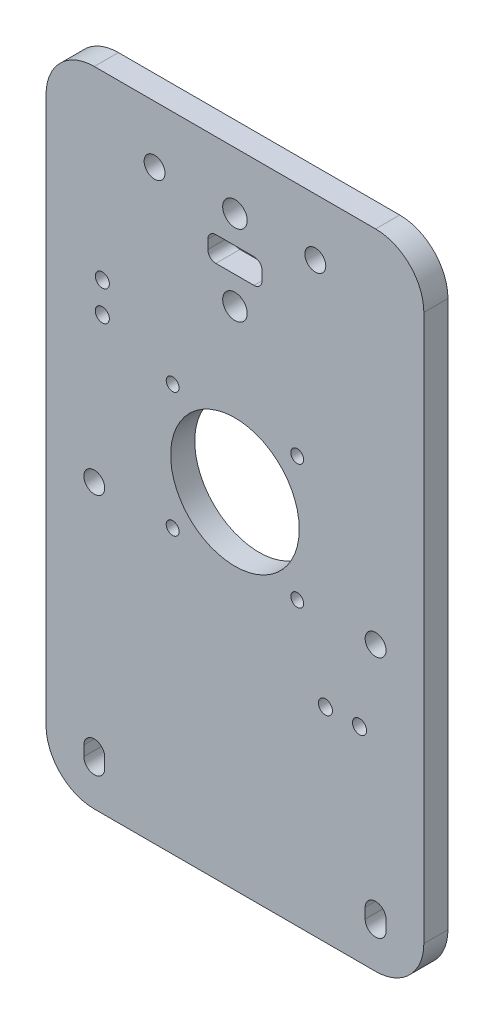
SolidWorks part; units mm, degrees
material "Acrylic (Medium-high impact)"
ref_plane "Спереди" through (0, 0, 0) normal (0, 0, 1) x (1, 0, 0)
ref_plane "Сверху" through (0, 0, 0) normal (0, 1, 0) x (1, 0, 0)
ref_plane "Справа" through (0, 0, 0) normal (1, 0, 0) x (0, 0, -1)
sketch "Model" plane through (0, 0, 0) normal (0, 0, 1) x (1, 0, 0)
  line L0 (-2.3021, 85.8) -> (5.2264, 85.8) construction
  line L1 (6.75, 135.8) -> (-6.75, 135.8) construction
  line L5 (0, 27.6115) -> (0, 21.6925) construction
  line L7 (-15.5, 9.9369) -> (-15.5, 9.0934) construction
  line L8 (15.5, 9.9369) -> (15.5, 9.0934) construction
  line L24 (-35, 37.2847) -> (-35, 77.3985) construction
  line L25 (-31.4983, 12.5) -> (-38.4, 12.5) construction
  line L26 (-31.4983, 10) -> (-38.4, 10) construction
  line L27 (-35, 12.5) -> (-35, 10) construction
  line L28 (-32.4, 12.5) -> (-32.4, 10)
  line L29 (-37.6, 12.5) -> (-37.6, 10)
  line L40 (31.4983, 10) -> (38.4, 10) construction
  line L41 (31.4983, 12.5) -> (38.4, 12.5) construction
  line L42 (35, 37.2847) -> (35, 77.3985) construction
  line L43 (35, 12.5) -> (35, 10) construction
  line L44 (32.4, 12.5) -> (32.4, 10)
  line L45 (37.6, 12.5) -> (37.6, 10)
  line L47 (-26.0102, 145.8) -> (26.0946, 145.8) construction
  line L48 (0, 129.408) -> (0, 90.7064) construction
  line L51 (-38.85, 70.45) -> (-29.8907, 70.45) construction
  line L53 (-16.3166, 125.8) -> (17.7871, 125.8) construction
  line L58 (38.85, 70.45) -> (29.8907, 70.45) construction
  line L4875 (-35, 160) -> (35, 160)
  line L4882 (47, 148) -> (47, 12)
  line L4889 (35, 0) -> (-35, 0)
  line L4896 (-47, 12) -> (-47, 148)
  line L5609 (6.75, 138.9) -> (-6.75, 138.9)
  line L5610 (-6.75, 138.9) -> (-6.75, 132.7)
  line L5611 (-6.75, 132.7) -> (6.75, 132.7)
  line L5612 (6.75, 132.7) -> (6.75, 138.9)
  line L6648 (-6.75, 138.9) -> (6.75, 138.9)
  line L6649 (6.75, 138.9) -> (6.75, 132.7)
  line L6650 (6.75, 132.7) -> (-6.75, 132.7)
  line L6651 (-6.75, 132.7) -> (-6.75, 138.9)
  arc A0 (-47, 12) -> (-35, 0) centre (-35, 12) ccw
  arc A1 (35, 0) -> (47, 12) centre (35, 12) ccw
  arc A2 (47, 148) -> (35, 160) centre (35, 148) ccw
  arc A3 (-35, 160) -> (-47, 148) centre (-35, 148) ccw
  circle A4 centre (0, 85.8) radius 16
  arc A13 (-32.4, 12.5) -> (-37.6, 12.5) centre (-35, 12.5) ccw
  arc A14 (-37.6, 10) -> (-32.4, 10) centre (-35, 10) ccw
  arc A19 (32.4, 12.5) -> (37.6, 12.5) centre (35, 12.5) cw
  arc A20 (37.6, 10) -> (32.4, 10) centre (35, 10) cw
  circle A29 centre (0, 145.8) radius 3.05
  circle A30 centre (-20, 145.8) radius 2.6
  circle A31 centre (20, 145.8) radius 2.6
  circle A32 centre (-35, 70.45) radius 2.6
  circle A33 centre (0, 125.8) radius 3.05
  circle A36 centre (35, 70.45) radius 2.6
  point P17 (0, 0)
  point P77 (-35, 11.25)
  point P114 (35, 11.25)
  point P127 (0, 160)
  dimension "D5" = 32
  dimension "D30" = 5.2
  dimension "D33" = 5.2
  dimension "D35" = 6.1
  dimension "D2" = 70
  dimension "D3" = 160
  dimension "D6" = 15.5
  dimension "D15" = 12
  dimension "D16" = 2.5
  dimension "D17" = 10
  dimension "D18" = 5.2
  dimension "D25" = 14.2
  dimension "D34" = 20
  dimension "D41" = 13.5
  dimension "D42" = 6.2
  dimension "D9" = 70
  dimension "D10" = 57.95
  dimension "D12" = 20
  dimension "D13" = 20
  dimension "D11" = 10
  dimension "D7" = 74.2
extrude "Base" add sketch "Model" along normal blind 6 contours L4875 A3 L4896 A0 L4889 A1 L4882 A2 L45 A20 L44 A19 region at (0, 158.1443, 0)
sketch "Sketch1" plane through (0, 0, 6) normal (0, 0, 1) x (1, 0, 0)
  line L1 (-35, 160) -> (35, 160) construction
  line L2 (-47, 12) -> (-47, 148) construction
  circle A0 centre (-33, 115) radius 1.75
  circle A1 centre (-33, 107.5) radius 1.75
  dimension "D1" = 3.5
  dimension "D3" = 7.5
  dimension "D4" = 14
  dimension "D5" = 45
extrude "SensorMount" cut sketch "Sketch1" against normal through all contours A1 | A0
sketch "Sketch2" plane through (0, 0, 6) normal (0, 0, 1) x (1, 0, 0)
  line L0 (35, 0) -> (-35, 0) construction
  line L1 (-47, 12) -> (-47, 148) construction
  circle A0 centre (22.5, 50.76) radius 1.75
  circle A1 centre (31, 50.76) radius 1.75
  dimension "D1" = 3.5
  dimension "D3" = 8.5
  dimension "D4" = 50.76
  dimension "D5" = 69.5
extrude "CableMount" cut sketch "Sketch2" against normal blind 10 contours A0 | A1
fillet "FilletCableSlot" radius 2 4 edges at (6.75, 138.9, 3) (-6.75, 138.9, 3) (-6.75, 132.7, 3) (6.75, 132.7, 3)
hole_wizard "Ø3.2 (3.2) Stepper mount Holes" positions "Sketch6" profile "Sketch7" hole size "Ø3.2" standard "ANSI Metric" end condition through all
sketch "Sketch6" plane through (0, 0, 6) normal (0, 0, 1) x (1, 0, 0)
  line L0 (-50.1491, 85.8) -> (50.1491, 85.8) construction
  line L2 (0, 0) -> (0, 95.4376) construction
  line L3 (35, 0) -> (-35, 0) construction
  circle A0 centre (0, 85.8) radius 16 construction
  point P0 (-15.5, 101.3)
  point P3 (-15.5, 70.3)
  point P6 (15.5, 70.3)
  point P9 (15.5, 101.3)
  point P22 (0, 85.8)
  dimension "D1" = 31
  dimension "D2" = 31
sketch "Sketch7" plane through (-15.5, 101.3, 6) normal (1, 0, 0) x (0, -1, 0)
  line L0 (0, 0) -> (0, 6)
  line L1 (0, 6) -> (1.6, 6)
  line L2 (1.6, 6) -> (1.6, 0)
  line L5 (1.6, 0) -> (0, 0)
  line L11 (0, -6.35) -> (0, 107.95) construction
  dimension "Thru Hole Dia." = 3.2
  dimension "Thru Hole Depth" = 6
equation "\"D11@Model\"=\"D34@Model\"/2"
